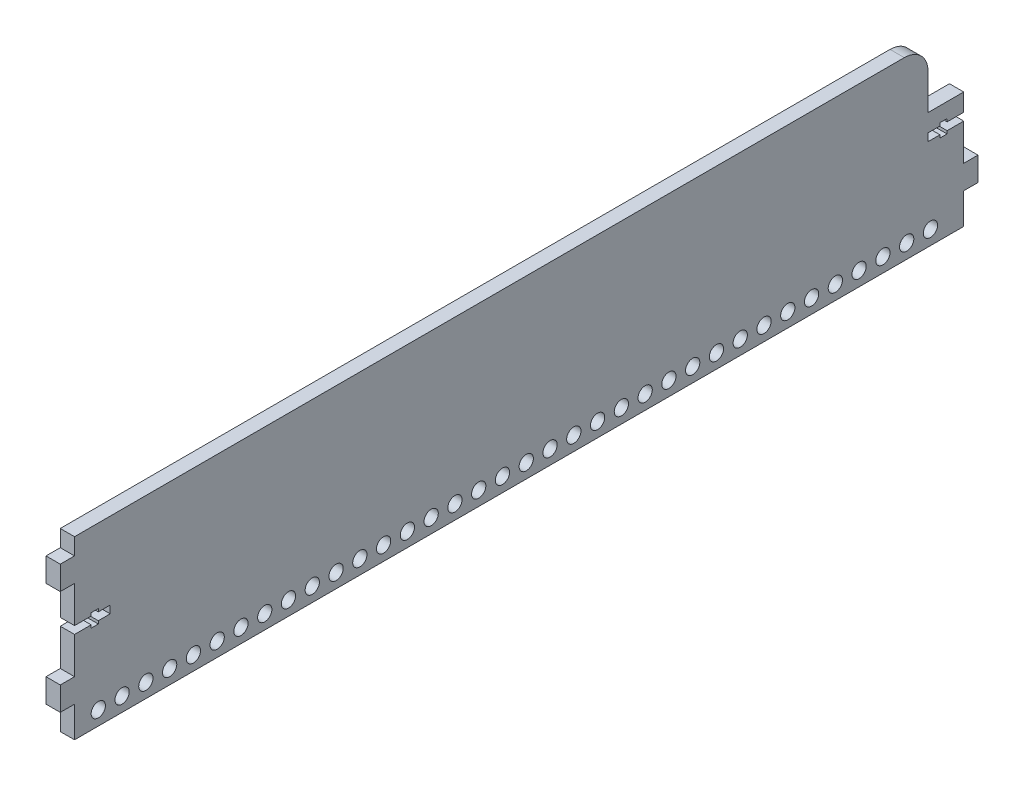
SolidWorks part; units mm, degrees
ref_plane "Front Plane" through (0, 0, 0) normal (0, 0, 1) x (1, 0, 0)
ref_plane "Top Plane" through (0, 0, 0) normal (0, 1, 0) x (1, 0, 0)
ref_plane "Right Plane" through (0, 0, 0) normal (1, 0, 0) x (0, 0, -1)
sketch "Sketch1" plane through (0, 0, 0) normal (1, 0, 0) x (0, 0, -1)
  line L1 (-187, -40) -> (187, -40)
  line L2 (-187, -40) -> (-187, 40)
  line L3 (-187, 40) -> (187, 40)
  line L4 (187, -40) -> (187, 40)
  line L5 (-187, -40) -> (187, 40) construction
  line L6 (-187, 40) -> (187, -40) construction
  point P0 (0, 0)
  dimension "D1" = 80
  dimension "D2" = 374
extrude "Boss-Extrude1" add sketch "Sketch1" along normal blind 6
sketch "Sketch4" plane through (0, 0, 187) normal (0, 0, 1) x (1, 0, 0)
  line L1 (6, 27) -> (0, 27) construction
  line L2 (6, 17) -> (6, 27) construction
  line L3 (0, 27) -> (0, 17) construction
  line L4 (0, 17) -> (6, 17) construction
  line L7 (6, -17) -> (0, -17) construction
  line L8 (6, -27) -> (6, -17) construction
  line L9 (0, -17) -> (0, -27) construction
  line L10 (0, -27) -> (6, -27) construction
  line L13 (6, 27) -> (0, 27)
  line L14 (6, 17) -> (6, 27)
  line L15 (0, 27) -> (0, 17)
  line L16 (0, 17) -> (6, 17)
  line L17 (6, -17) -> (0, -17)
  line L18 (6, -27) -> (6, -17)
  line L19 (0, -17) -> (0, -27)
  line L20 (0, -27) -> (6, -27)
extrude "Boss-Extrude2" add sketch "Sketch4" along normal blind 6
sketch "Sketch5" plane through (0, 0, 0) normal (-1, 0, 0) x (0, 0, 1)
  line L0 (187, 17) -> (187, -17) construction
  line L7 (0, 0) -> (0, -20.5925) construction
  line L8 (-187, 1.6) -> (-180, 1.6)
  line L9 (-177, 2.8) -> (-180, 2.8)
  line L10 (-177, 1.6) -> (-172, 1.6)
  line L11 (-172, -1.6) -> (-172, 1.6)
  line L12 (-177, -1.6) -> (-172, -1.6)
  line L13 (-177, -2.8) -> (-180, -2.8)
  line L14 (-187, -1.6) -> (-180, -1.6)
  line L15 (-180, -2.8) -> (-180, -1.6)
  line L16 (-180, 1.6) -> (-180, 2.8)
  line L17 (-177, 1.6) -> (-177, 2.8)
  line L18 (-177, -2.8) -> (-177, -1.6)
  line L19 (193, -1.6) -> (193, 1.6) construction
  line L20 (193, -1.6) -> (193, 1.6)
  line L21 (193, 0) -> (146.4296, 0) construction
  line L25 (187, -1.6) -> (187, 1.6)
  line L26 (177, -2.8) -> (177, -1.6)
  line L27 (177, 1.6) -> (177, 2.8)
  line L28 (180, 1.6) -> (180, 2.8)
  line L29 (180, -2.8) -> (180, -1.6)
  line L30 (187, -1.6) -> (180, -1.6)
  line L31 (177, -2.8) -> (180, -2.8)
  line L32 (177, -1.6) -> (172, -1.6)
  line L33 (172, -1.6) -> (172, 1.6)
  line L34 (177, 1.6) -> (172, 1.6)
  line L35 (177, 2.8) -> (180, 2.8)
  line L36 (187, 1.6) -> (180, 1.6)
  line L37 (-187, -1.6) -> (-187, 1.6)
  line L38 (-193, -1.6) -> (-193, 1.6)
  point P0 (187, 0)
  dimension "D1" = 15
  dimension "D2" = 5.6
  dimension "D3" = 3.2
  dimension "D4" = 7
  dimension "D5" = 3
extrude "Cut-Extrude3" cut sketch "Sketch5" against normal up to next contours L25 L36 L28 L35 L27 L34 L33 L32 L26 L31 L29 L30 | L37 L14 L15 L13 L18 L12 L11 L10 L17 L9 L16 L8 region at (0, 0, -179.3696) region at (0, 0, 179.3696)
sketch "Sketch7" plane through (0, 0, -187) normal (0, 0, -1) x (-1, 0, 0)
  line L6 (-6, -17) -> (0, -17)
  line L7 (-6, -17) -> (-6, -27)
  line L8 (-6, -27) -> (0, -27)
  line L9 (0, -17) -> (0, -27)
  line L15 (-6, -40) -> (-6, -1.6) construction
  line L16 (0, -40) -> (0, -1.6) construction
  line L17 (-6, -17) -> (0, -17) construction
  line L18 (0, -27) -> (-6, -27) construction
extrude "Boss-Extrude3" add sketch "Sketch7" along normal blind 6
sketch "Sketch8" plane through (0, 40, 0) normal (0, 1, 0) x (1, 0, 0)
  line L1 (0, 187) -> (6, 187)
  line L2 (0, 187) -> (0, -187)
  line L3 (0, -187) -> (6, -187)
  line L4 (6, 187) -> (6, -187)
extrude "Cut-Extrude4" cut sketch "Sketch8" against normal blind 6
sketch "Sketch9" plane through (0, 34, 0) normal (0, 1, 0) x (1, 0, 0)
  line L0 (0, 187) -> (0, -187) construction
  line L1 (0, 187) -> (6, 187)
  line L2 (0, 187) -> (0, 172)
  line L3 (0, 172) -> (6, 172)
  line L4 (6, 187) -> (6, 172)
  line L5 (6, -187) -> (6, 187) construction
  dimension "D2" = 15
extrude "Cut-Extrude5" cut sketch "Sketch9" against normal blind 25
fillet "Fillet1" radius 10 1 edges at (3, 34, -172)
sketch "Sketch10" plane through (0, 0, 0) normal (-1, 0, 0) x (0, 0, 1)
  line L0 (187, -40) -> (-187, -40) construction
  line L1 (187, -27) -> (187, -40) construction
  circle A0 centre (177, -34) radius 3
  circle A1 centre (167, -34) radius 3
  circle A2 centre (157, -34) radius 3
  circle A3 centre (147, -34) radius 3
  circle A4 centre (137, -34) radius 3
  circle A5 centre (127, -34) radius 3
  circle A6 centre (117, -34) radius 3
  circle A7 centre (107, -34) radius 3
  circle A8 centre (97, -34) radius 3
  circle A9 centre (87, -34) radius 3
  circle A10 centre (77, -34) radius 3
  circle A11 centre (67, -34) radius 3
  circle A12 centre (57, -34) radius 3
  circle A13 centre (47, -34) radius 3
  circle A14 centre (37, -34) radius 3
  circle A15 centre (27, -34) radius 3
  circle A16 centre (17, -34) radius 3
  circle A17 centre (7, -34) radius 3
  circle A18 centre (-3, -34) radius 3
  circle A19 centre (-13, -34) radius 3
  circle A20 centre (-23, -34) radius 3
  circle A21 centre (-33, -34) radius 3
  circle A22 centre (-43, -34) radius 3
  circle A23 centre (-53, -34) radius 3
  circle A24 centre (-63, -34) radius 3
  circle A25 centre (-73, -34) radius 3
  circle A26 centre (-83, -34) radius 3
  circle A27 centre (-93, -34) radius 3
  circle A28 centre (-103, -34) radius 3
  circle A29 centre (-113, -34) radius 3
  circle A30 centre (-123, -34) radius 3
  circle A31 centre (-133, -34) radius 3
  circle A32 centre (-143, -34) radius 3
  circle A33 centre (-153, -34) radius 3
  circle A34 centre (-163, -34) radius 3
  circle A35 centre (-173, -34) radius 3
  dimension "D1" = 6
  dimension "D2" = 6
  dimension "D3" = 10
  dimension "D4" = 36
extrude "Cut-Extrude6" cut sketch "Sketch10" against normal up to next (6 mm away)
